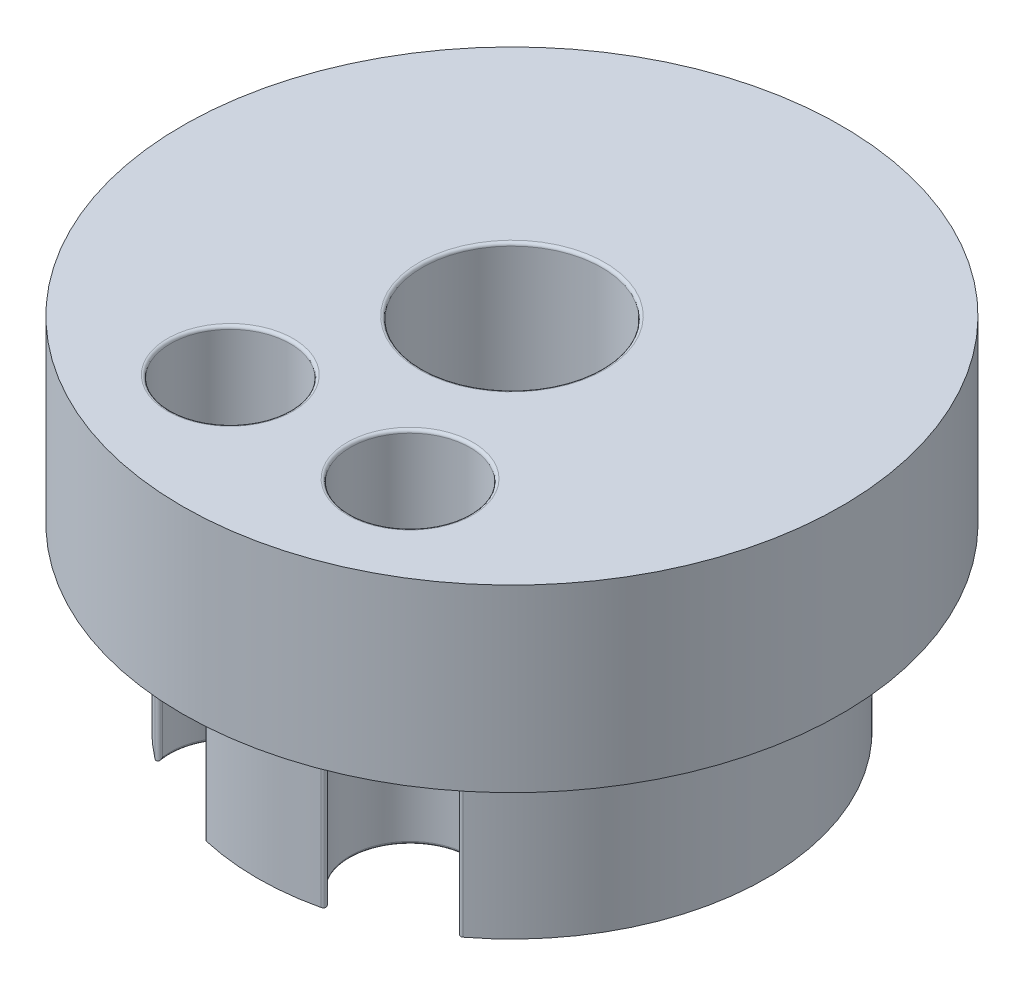
SolidWorks part; units mm, degrees
ref_plane "Front Plane" through (0, 0, 0) normal (0, 0, 1) x (1, 0, 0)
ref_plane "Top Plane" through (0, 0, 0) normal (0, 1, 0) x (1, 0, 0)
ref_plane "Right Plane" through (0, 0, 0) normal (1, 0, 0) x (0, 0, -1)
sketch "Sketch1" plane through (0, 0, 0) normal (0, 1, 0) x (1, 0, 0)
  circle A0 centre (0, 0) radius 0.55
  dimension "D1" = 1.1
extrude "Boss-Extrude1" add sketch "Sketch1" against normal blind 0.3
sketch "Sketch2" plane through (0, -0.3, 0) normal (0, -1, 0) x (1, 0, 0)
  circle A0 centre (0, 0) radius 0.425
  dimension "D1" = 0.85
extrude "Boss-Extrude2" add sketch "Sketch2" along normal blind 0.3
sketch "Sketch3" plane through (0, 0, 0) normal (0, 1, 0) x (1, 0, 0)
  line L0 (0, 0) -> (0, -0.425) construction
  line L1 (-0.15, -0.32) -> (0.15, -0.32) construction
  circle A0 centre (0, 0) radius 0.15
  circle A1 centre (0, 0) radius 0.425 construction
  circle A2 centre (0, 0) radius 0.425 construction
  circle A3 centre (0.15, -0.32) radius 0.1
  circle A4 centre (-0.15, -0.32) radius 0.1
  dimension "D1" = 0.3
  dimension "D4" = 0.32
  dimension "D5" = 0.2
  dimension "D2" = 0.15
  dimension "D3" = 0.15
extrude "Cut-Extrude1" cut sketch "Sketch3" against normal through all
fillet "Fillet5" radius 0.005 12 edges at (0, 0, 0.15) (0, -0.6, 0.15) (0.15, 0, 0.42) (0.1076, -0.6, 0.2295) (-0.15, 0, 0.42) (-0.1076, -0.6, 0.2295) (0.2465, -0.45, 0.3462) (0.1084, -0.45, 0.4109) (0.1924, -0.3, 0.4105) (-0.1084, -0.45, 0.4109) (-0.2465, -0.45, 0.3462) (-0.1924, -0.3, 0.4105)
